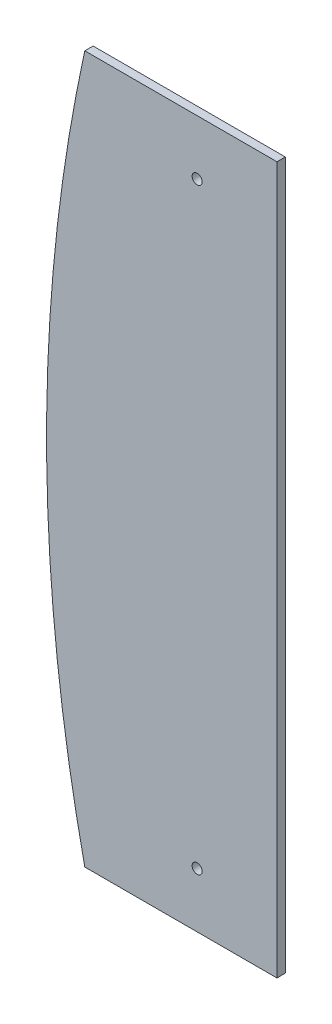
SolidWorks part; units mm, degrees
material "SA-283 Gr.C"
ref_plane "Front Plane" through (0, 0, 0) normal (0, 0, 1) x (1, 0, 0)
ref_plane "Top Plane" through (0, 0, 0) normal (0, 1, 0) x (1, 0, 0)
ref_plane "Right Plane" through (0, 0, 0) normal (1, 0, 0) x (0, 0, -1)
sketch "Sketch1" plane through (0, 0, 0) normal (0, 0, 1) x (1, 0, 0)
  line B0 (80.3469, 415.7192) -> (-150.7167, 415.7192)
  line B1 (80.3469, -434.2808) -> (80.3469, 415.7192)
  line B2 (80.3469, -434.2808) -> (-150.7167, -434.2808)
  arc B3 (-150.7167, 415.7192) -> (-150.7167, -434.2808) centre (1792.3469, -9.2808) ccw
  line B4 (-196.6531, -9.2808) -> (1792.3469, -9.2808) construction
sketch_block_instance "Silencer support plate-1"
sketch_block "Silencer support plate" parameters "D2"=1989, "D3"=1989, "D1"=900, "D4"=91, "D5"=718, "D6"=96, "D7"=231.378
extrude "Boss-Extrude1" add sketch "Sketch1" along normal blind 10 contours B0 B3 B2 B1 region at (-50.8898, -9.2808, 0)
hole_wizard "Ø12.0mm Dowel Hole1" positions "3DSketch1" profile "Sketch2" hole size "Ø12.0" standard "ANSI Metric" end condition through all
sketch3d "3DSketch1"
  point P0 (-15.6531, 349.7192, 0)
  point P3 (-15.6531, -368.2808, 0)
  point P6 (-15.6531, 349.7192, 0)
  point P8 (-15.6531, 349.7192, 0)
  point P10 (-15.6531, -368.2808, 0)
  point P13 (-15.6531, -368.2808, 0)
  point P15 (-15.6531, 349.7192, 0)
sketch "Sketch2" plane through (-15.6531, 349.7192, 0) normal (1, 0, 0) x (0, 1, 0)
  line L0 (0, 0) -> (0, 10)
  line L1 (0, 10) -> (6, 10)
  line L2 (6, 10) -> (6, 0)
  line L5 (6, 0) -> (0, 0)
  line L11 (0, -6.35) -> (0, 107.95) construction
  dimension "Thru Hole Dia." = 12
  dimension "Thru Hole Depth" = 10
